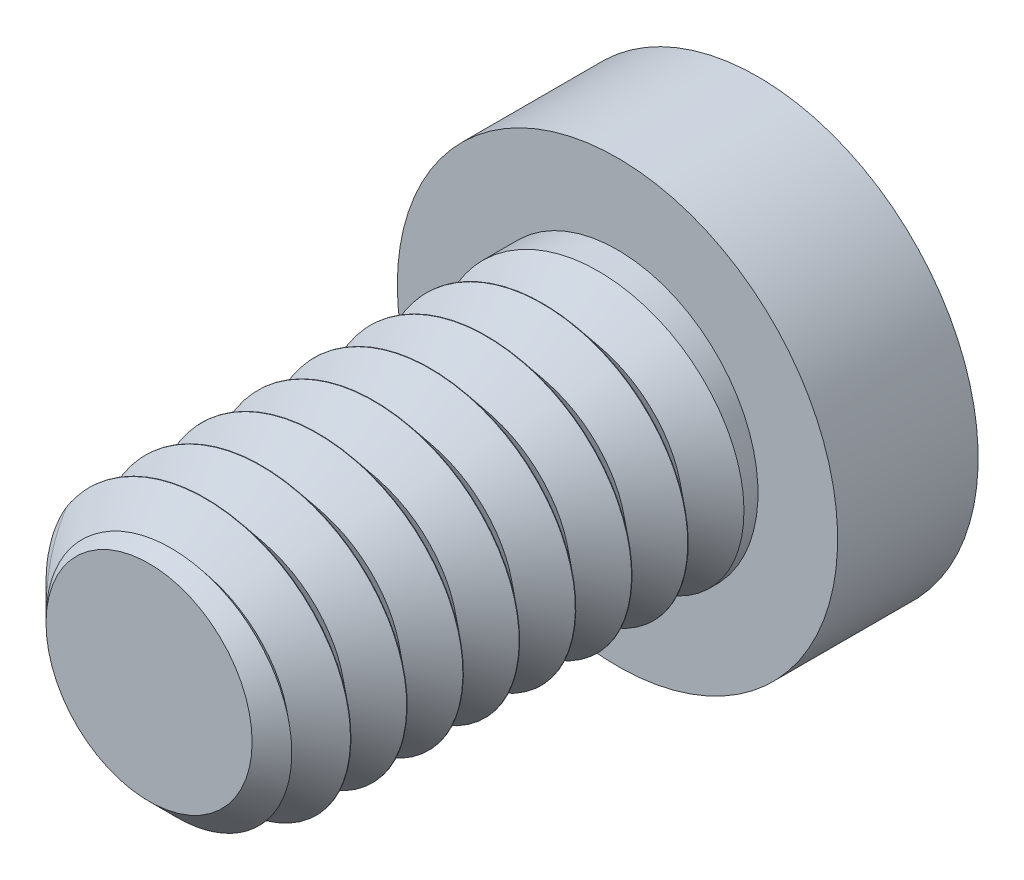
SolidWorks part; units mm, degrees
ref_plane "Front Plane" through (0, 0, 0) normal (0, 0, 1) x (1, 0, 0)
ref_plane "Top Plane" through (0, 0, 0) normal (0, 1, 0) x (1, 0, 0)
ref_plane "Right Plane" through (0, 0, 0) normal (1, 0, 0) x (0, 0, -1)
sketch "Sketch1" plane through (0, 0, 0) normal (0, 0, 1) x (1, 0, 0)
  circle A0 centre (0, 0) radius 3
  dimension "D1" = 6
extrude "Boss-Extrude1" add sketch "Sketch1" along normal blind 10
ref_plane "Plane4" through (0, 0, 0.6) normal (0, 0, 1) x (1, 0, 0)
chamfer "Chamfer3" distance 0.8 angle 45 1 edges at (3, 0, 10)
sketch "Sketch2" plane through (0, 0, 0.6) normal (0, 0, -1) x (-1, 0, 0)
  circle A0 centre (0, 0) radius 3
  circle A2 centre (0, 0) radius 3 construction
curve "Helix/Spiral1" pitch 1.2 height 35 turns 29.1667
sketch "Sketch3" plane through (0, 0, 0) normal (1, 0, 0) x (0, 0, -1)
  line L0 (-1.195, -3) -> (-0.005, -3)
  line L1 (-0.005, -3) -> (-0.6, -2.28)
  line L2 (-0.6, -2.28) -> (-1.195, -3)
  line L3 (-0.01, -3) -> (-9.2, -3) construction
  line L4 (-0.6, 5.17) -> (-0.6, -5.17) construction
  point P3 (-0.6, -3)
  dimension "D2" = 0.72
  dimension "D1" = 1.19
sweep "Cut-Sweep3" cut profiles "Sketch3" path "Helix/Spiral1" align with end faces yes
sketch "Sketch5" plane through (0, 0, 0) normal (0, 0, -1) x (-1, 0, 0)
  circle A0 centre (0, 0) radius 4.7
  dimension "D1" = 9.4
extrude "Boss-Extrude2" add sketch "Sketch5" along normal blind 3
sketch "Sketch4" plane through (0, 0, -3) normal (0, 0, -1) x (-1, 0, 0)
  line L21 (1.04, -1.04) -> (-1.04, -1.04)
  line L22 (1.04, -1.04) -> (1.04, 1.04)
  line L23 (1.04, 1.04) -> (-1.04, 1.04)
  line L24 (-1.04, -1.04) -> (-1.04, 1.04)
  line L25 (1.04, -1.04) -> (-1.04, 1.04) construction
  line L26 (1.04, 1.04) -> (-1.04, -1.04) construction
  point P0 (0, 0)
  point P6 (0, 0)
  dimension "D1" = 2.08
extrude "Cut-Extrude1" cut sketch "Sketch4" against normal blind 5 draft 1
equation "\"cleatShaftLen\" = 3"
equation "\"cleatHeadLen\" = 4mm"
equation "\"cleatHeadGirth\" = 12mm"
equation "\"cleatShaftGirth\" = 8mm"
equation "\"cleatTolOffset\" = 0.4mm"
equation "\"cleatCham\" = 1mm"
equation "\"cleatSpacing\" = 30mm"
equation "\"cleatTriangleAngle\" = 25deg"
equation "\"cleatMinimumTriangleAngle\" = 12deg"
equation "\"nCleats\" = 2"
equation "\"threadID\" = 8.3mm"
equation "\"threadPitch\" = 2mm"
equation "\"threadOD\" = 10.7mm"
equation "\"cleatFemShaftLen\" = \"cleatShaftLen\" - \"cleatTolOffset\""
equation "\"cleatFemHeadLen\" = \"cleatHeadLen\" + \"cleatTolOffset\" * 1.25"
equation "\"cleatFemHeadGirth\" = \"cleatHeadGirth\" + \"cleatTolOffset\""
equation "\"cleatFemShaftGirth\" = \"cleatShaftGirth\" + \"cleatTolOffset\""
equation "\"lip\" = 2mm"
equation "\"cubeCham\" = 0.7mm"
equation "\"cubeCutoutPadding\" = 3mm"
equation "\"wall\" = 3mm"
equation "\"cleatLen\" = \"cleatShaftLen\" + \"cleatHeadLen\""
equation "\"coverThickness\" = 2mm"
equation "\"plugDepth\" = 4mm"
equation "\"bottomChamOffset\" = 1.8mm"
equation "\"maleHelperAngle\" = 45deg"
equation "\"maleHelperAngle2\" = 35deg"
equation "\"stFactor\" = 0.6"
equation "\"stID\" = \"threadID\" * \"stFactor\""
equation "\"stOD\" = \"threadOD\" * \"stFactor\""
equation "\"stPitch\" = \"threadPitch\" * \"stFactor\""
equation "\"temp\" = 0"
equation "\"threadMaleOD\" = 10.0mm"
equation "\"stMaleOD\" = \"threadMaleOD\" * \"stFactor\""
equation "\"D1@Sketch1\"=\"stMaleOD\""
equation "\"D1@Boss-Extrude1\"=10mm"
equation "\"D2@Sketch3\"=(\"stOD\"-\"stID\")/2"
equation "\"D1@Sketch3\"=\"stPitch\"-0.01"
equation "\"D1@Boss-Extrude2\"= \"stSocketHeadLen\""
equation "\"stProtrusion\" = (\"stOD\" - \"stID\") / 2"
equation "\"stHexDiam\" = 2.5mm"
equation "\"stHexPad\" = 0.08mm"
equation "\"stSocketHeadProtrusion\" = 0.65mm"
equation "\"stSocketHeadLen\" = 1.2mm"
equation "\"stSocketHeadLenPad\" = 0.1mm"
equation "\"stSocketHeadCounterboreDepth\" = \"stSocketHeadLen\" + \"stSocketHeadLenPad\""
equation "\"stDriverDepth\" = 2mm"
equation "\"stNutODPad\" = 3mm"
equation "\"stNutDiam\" = \"stOD\" + \"stNutODPad\""
equation "\"stNutHeight\" = 3mm"
equation "\"stNutCham\" = 0.4mm"
equation "\"stSocketHeadDiam\" = \"stOD\" + \"stSocketHeadProtrusion\""
equation "\"threadMaleSocketDiam\" = 15.0mm"
equation "\"threadMaleHex\" = 6mm"
equation "\"wall2\" = 4.15mm"
equation "\"plugCornerFill\" = 3mm"
